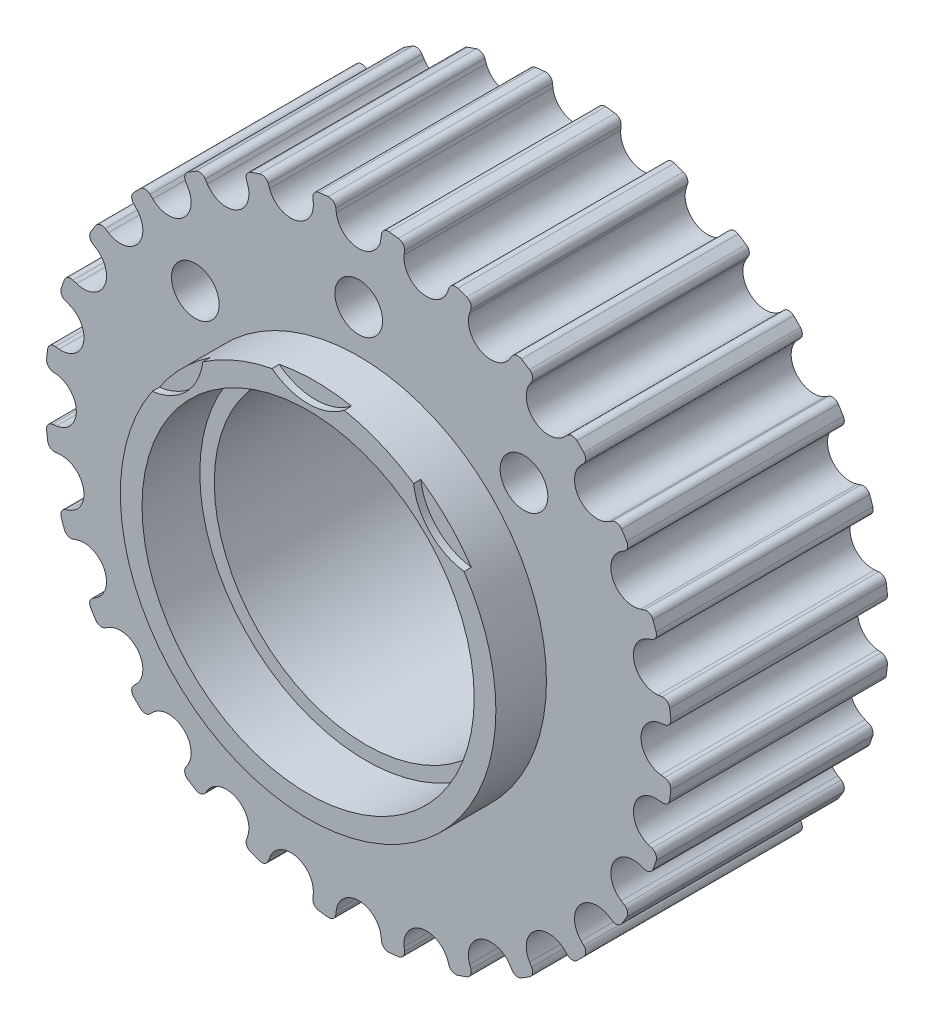
SolidWorks part; units mm, degrees
note: The reader was unsure of these and kept them because the rebuilt part matched: shared geometry of "草图15<2>".
ref_plane "前视基准面" through (0, 0, 0) normal (0, 0, 1) x (1, 0, 0)
ref_plane "上视基准面" through (0, 0, 0) normal (0, 1, 0) x (1, 0, 0)
ref_plane "右视基准面" through (0, 0, 0) normal (1, 0, 0) x (0, 0, -1)
sketch "草图2" plane through (0, 0, 0) normal (0, 0, 1) x (1, 0, 0)
  line L36 (1.3319, 20.7804) -> (1.2989, 20.5118)
  line L37 (-1.7978, 20.5118) -> (-1.8308, 20.7804)
  line L38 (-3.4222, 20.6011) -> (-3.3946, 20.3319)
  line L39 (-6.4137, 19.6428) -> (-6.5056, 19.8973)
  line L40 (-8.0172, 19.3684) -> (-7.9303, 19.1121)
  line L41 (-10.7204, 17.7684) -> (-10.8667, 17.9962)
  line L42 (-12.2227, 17.1441) -> (-12.081, 16.9135)
  line L43 (-14.5021, 14.9827) -> (-14.6954, 15.1722)
  line L44 (-15.8278, 14.0398) -> (-15.6383, 13.8465)
  line L45 (-17.5691, 11.4254) -> (-17.7997, 11.5671)
  line L46 (-18.6517, 10.2111) -> (-18.424, 10.0648)
  line L47 (-19.7676, 7.2748) -> (-20.024, 7.3616)
  line L48 (-20.5529, 5.85) -> (-20.2983, 5.7581)
  line L49 (-20.9874, 2.739) -> (-21.2567, 2.7666)
  line L50 (-21.436, 1.1752) -> (-21.1673, 1.1423)
  line L51 (-21.1673, -1.9545) -> (-21.436, -1.9875)
  line L52 (-21.2567, -3.5789) -> (-20.9874, -3.5512)
  line L53 (-20.2983, -6.5703) -> (-20.5529, -6.6623)
  line L54 (-20.024, -8.1739) -> (-19.7676, -8.087)
  line L55 (-18.424, -10.8771) -> (-18.6517, -11.0234)
  line L56 (-17.7997, -12.3793) -> (-17.5691, -12.2376)
  line L57 (-15.6383, -14.6588) -> (-15.8278, -14.8521)
  line L58 (-14.6954, -15.9845) -> (-14.5021, -15.795)
  line L59 (-12.081, -17.7258) -> (-12.2227, -17.9564)
  line L60 (-10.8667, -18.8084) -> (-10.7204, -18.5807)
  line L61 (-7.9303, -19.9243) -> (-8.0172, -20.1806)
  line L62 (-6.5056, -20.7096) -> (-6.4137, -20.455)
  line L63 (-3.3946, -21.1441) -> (-3.4222, -21.4133)
  line L64 (-1.8308, -21.5926) -> (-1.7978, -21.324)
  line L65 (1.2989, -21.324) -> (1.3319, -21.5926)
  line L66 (2.9233, -21.4133) -> (2.8957, -21.1441)
  line L67 (5.9148, -20.455) -> (6.0067, -20.7096)
  line L68 (7.5183, -20.1806) -> (7.4314, -19.9243)
  line L69 (10.2215, -18.5807) -> (10.3678, -18.8084)
  line L70 (11.7238, -17.9564) -> (11.5821, -17.7258)
  line L71 (14.0032, -15.795) -> (14.1965, -15.9845)
  line L72 (15.3289, -14.8521) -> (15.1394, -14.6588)
  line L73 (17.0702, -12.2376) -> (17.3008, -12.3793)
  line L74 (18.1528, -11.0234) -> (17.9251, -10.8771)
  line L75 (19.2687, -8.087) -> (19.5251, -8.1739)
  line L76 (20.054, -6.6623) -> (19.7994, -6.5703)
  line L77 (20.4885, -3.5512) -> (20.7578, -3.5789)
  line L78 (20.9371, -1.9875) -> (20.6684, -1.9545)
  line L79 (20.6684, 1.1423) -> (20.9371, 1.1752)
  line L80 (20.7578, 2.7666) -> (20.4885, 2.739)
  line L81 (19.7994, 5.7581) -> (20.054, 5.85)
  line L82 (19.5251, 7.3616) -> (19.2687, 7.2748)
  line L83 (17.9251, 10.0648) -> (18.1528, 10.2111)
  line L84 (17.3008, 11.5671) -> (17.0702, 11.4254)
  line L85 (15.1394, 13.8465) -> (15.3289, 14.0398)
  line L86 (14.1965, 15.1722) -> (14.0032, 14.9827)
  line L87 (11.5821, 16.9135) -> (11.7238, 17.1441)
  line L88 (10.3678, 17.9962) -> (10.2215, 17.7684)
  line L89 (7.4314, 19.1121) -> (7.5183, 19.3684)
  line L90 (6.0067, 19.8973) -> (5.9148, 19.6428)
  line L91 (2.8957, 20.3319) -> (2.9233, 20.6011)
  circle A72 centre (-0.2458, -0.3677) radius 12 construction
  circle A73 centre (-0.2458, -0.3677) radius 10.5
  arc A74 (2.9233, 20.6011) -> (2.5067, 21.1262) centre (2.4458, 20.6501) ccw
  arc A75 (2.5067, 21.1262) -> (1.8549, 21.1996) centre (-0.2495, -0.4061) ccw
  arc A76 (1.8549, 21.1996) -> (1.3319, 20.7804) centre (1.8083, 20.7219) ccw
  arc A77 (-1.7978, 20.5118) -> (1.2989, 20.5118) centre (-0.2495, 20.7019) ccw
  arc A78 (-1.8308, 20.7804) -> (-2.3538, 21.1996) centre (-2.3072, 20.7219) ccw
  arc A79 (-2.3538, 21.1996) -> (-3.0056, 21.1262) centre (-0.2495, -0.4061) ccw
  arc A80 (-3.0056, 21.1262) -> (-3.4222, 20.6011) centre (-2.9447, 20.6501) ccw
  arc A81 (-6.4137, 19.6428) -> (-3.3946, 20.3319) centre (-4.9464, 20.1727) ccw
  arc A82 (-6.5056, 19.8973) -> (-7.1087, 20.1897) centre (-6.9571, 19.7343) ccw
  arc A83 (-7.1087, 20.1897) -> (-7.7279, 19.973) centre (-0.2495, -0.4061) ccw
  arc A84 (-7.7279, 19.973) -> (-8.0172, 19.3684) centre (-7.5626, 19.5224) ccw
  arc A85 (-10.7204, 17.7684) -> (-7.9303, 19.1121) centre (-9.4079, 18.6115) ccw
  arc A86 (-10.8667, 17.9962) -> (-11.5198, 18.147) centre (-11.2706, 17.7367) ccw
  arc A87 (-11.5198, 18.147) -> (-12.0752, 17.798) centre (-0.2495, -0.4061) ccw
  arc A88 (-12.0752, 17.798) -> (-12.2227, 17.1441) centre (-11.8137, 17.3954) ccw
  arc A89 (-14.5021, 14.9827) -> (-12.081, 16.9135) centre (-13.4101, 16.0968) ccw
  arc A90 (-14.6954, 15.1722) -> (-15.3656, 15.1739) centre (-15.0314, 14.8294) ccw
  arc A91 (-15.3656, 15.1739) -> (-15.8295, 14.7101) centre (-0.2495, -0.4061) ccw
  arc A92 (-15.8295, 14.7101) -> (-15.8278, 14.0398) centre (-15.485, 14.3758) ccw
  arc A93 (-17.5691, 11.4254) -> (-15.6383, 13.8465) centre (-16.7524, 12.7545) ccw
  arc A94 (-17.7997, 11.5671) -> (-18.4535, 11.4196) centre (-18.051, 11.1582) ccw
  arc A95 (-18.4535, 11.4196) -> (-18.8026, 10.8642) centre (-0.2495, -0.4061) ccw
  arc A96 (-18.8026, 10.8642) -> (-18.6517, 10.2111) centre (-18.3923, 10.615) ccw
  arc A97 (-19.7676, 7.2748) -> (-18.424, 10.0648) centre (-19.2671, 8.7523) ccw
  arc A98 (-20.024, 7.3616) -> (-20.6286, 7.0724) centre (-20.178, 6.907) ccw
  arc A99 (-20.6286, 7.0724) -> (-20.8453, 6.4532) centre (-0.2495, -0.4061) ccw
  arc A100 (-20.8453, 6.4532) -> (-20.5529, 5.85) centre (-20.3899, 6.3015) ccw
  arc A101 (-20.9874, 2.739) -> (-20.2983, 5.7581) centre (-20.8282, 4.2909) ccw
  arc A102 (-21.2567, 2.7666) -> (-21.7818, 2.3501) centre (-21.3057, 2.2891) ccw
  arc A103 (-21.7818, 2.3501) -> (-21.8552, 1.6982) centre (-0.2495, -0.4061) ccw
  arc A104 (-21.8552, 1.6982) -> (-21.436, 1.1752) centre (-21.3775, 1.6517) ccw
  arc A105 (-21.1673, -1.9545) -> (-21.1673, 1.1423) centre (-21.3575, -0.4061) ccw
  arc A106 (-21.436, -1.9875) -> (-21.8552, -2.5104) centre (-21.3775, -2.4639) ccw
  arc A107 (-21.8552, -2.5104) -> (-21.7818, -3.1623) centre (-0.2495, -0.4061) ccw
  arc A108 (-21.7818, -3.1623) -> (-21.2567, -3.5789) centre (-21.3057, -3.1014) ccw
  arc A109 (-20.2983, -6.5703) -> (-20.9874, -3.5512) centre (-20.8282, -5.1031) ccw
  arc A110 (-20.5529, -6.6623) -> (-20.8453, -7.2654) centre (-20.3899, -7.1137) ccw
  arc A111 (-20.8453, -7.2654) -> (-20.6286, -7.8846) centre (-0.2495, -0.4061) ccw
  arc A112 (-20.6286, -7.8846) -> (-20.024, -8.1739) centre (-20.178, -7.7192) ccw
  arc A113 (-18.424, -10.8771) -> (-19.7676, -8.087) centre (-19.2671, -9.5645) ccw
  arc A114 (-18.6517, -11.0234) -> (-18.8026, -11.6764) centre (-18.3923, -11.4272) ccw
  arc A115 (-18.8026, -11.6764) -> (-18.4535, -12.2319) centre (-0.2495, -0.4061) ccw
  arc A116 (-18.4535, -12.2319) -> (-17.7997, -12.3793) centre (-18.051, -11.9704) ccw
  arc A117 (-15.6383, -14.6588) -> (-17.5691, -12.2376) centre (-16.7524, -13.5667) ccw
  arc A118 (-15.8278, -14.8521) -> (-15.8295, -15.5223) centre (-15.485, -15.1881) ccw
  arc A119 (-15.8295, -15.5223) -> (-15.3656, -15.9862) centre (-0.2495, -0.4061) ccw
  arc A120 (-15.3656, -15.9862) -> (-14.6954, -15.9845) centre (-15.0314, -15.6417) ccw
  arc A121 (-12.081, -17.7258) -> (-14.5021, -15.795) centre (-13.4101, -16.909) ccw
  arc A122 (-12.2227, -17.9564) -> (-12.0752, -18.6102) centre (-11.8137, -18.2077) ccw
  arc A123 (-12.0752, -18.6102) -> (-11.5198, -18.9592) centre (-0.2495, -0.4061) ccw
  arc A124 (-11.5198, -18.9592) -> (-10.8667, -18.8084) centre (-11.2706, -18.549) ccw
  arc A125 (-7.9303, -19.9243) -> (-10.7204, -18.5807) centre (-9.4079, -19.4238) ccw
  arc A126 (-8.0172, -20.1806) -> (-7.7279, -20.7853) centre (-7.5626, -20.3347) ccw
  arc A127 (-7.7279, -20.7853) -> (-7.1087, -21.0019) centre (-0.2495, -0.4061) ccw
  arc A128 (-7.1087, -21.0019) -> (-6.5056, -20.7096) centre (-6.9571, -20.5465) ccw
  arc A129 (-3.3946, -21.1441) -> (-6.4137, -20.455) centre (-4.9464, -20.9849) ccw
  arc A130 (-3.4222, -21.4133) -> (-3.0056, -21.9384) centre (-2.9447, -21.4623) ccw
  arc A131 (-3.0056, -21.9384) -> (-2.3538, -22.0119) centre (-0.2495, -0.4061) ccw
  arc A132 (-2.3538, -22.0119) -> (-1.8308, -21.5926) centre (-2.3072, -21.5341) ccw
  arc A133 (1.2989, -21.324) -> (-1.7978, -21.324) centre (-0.2495, -21.5141) ccw
  arc A134 (1.3319, -21.5926) -> (1.8549, -22.0119) centre (1.8083, -21.5341) ccw
  arc A135 (1.8549, -22.0119) -> (2.5067, -21.9384) centre (-0.2495, -0.4061) ccw
  arc A136 (2.5067, -21.9384) -> (2.9233, -21.4133) centre (2.4458, -21.4623) ccw
  arc A137 (5.9148, -20.455) -> (2.8957, -21.1441) centre (4.4475, -20.9849) ccw
  arc A138 (6.0067, -20.7096) -> (6.6098, -21.0019) centre (6.4582, -20.5465) ccw
  arc A139 (6.6098, -21.0019) -> (7.229, -20.7853) centre (-0.2495, -0.4061) ccw
  arc A140 (7.229, -20.7853) -> (7.5183, -20.1806) centre (7.0637, -20.3347) ccw
  arc A141 (10.2215, -18.5807) -> (7.4314, -19.9243) centre (8.909, -19.4238) ccw
  arc A142 (10.3678, -18.8084) -> (11.0209, -18.9592) centre (10.7716, -18.549) ccw
  arc A143 (11.0209, -18.9592) -> (11.5763, -18.6102) centre (-0.2495, -0.4061) ccw
  arc A144 (11.5763, -18.6102) -> (11.7238, -17.9564) centre (11.3148, -18.2077) ccw
  arc A145 (14.0032, -15.795) -> (11.5821, -17.7258) centre (12.9112, -16.909) ccw
  arc A146 (14.1965, -15.9845) -> (14.8667, -15.9862) centre (14.5325, -15.6417) ccw
  arc A147 (14.8667, -15.9862) -> (15.3306, -15.5223) centre (-0.2495, -0.4061) ccw
  arc A148 (15.3306, -15.5223) -> (15.3289, -14.8521) centre (14.9861, -15.1881) ccw
  arc A149 (17.0702, -12.2376) -> (15.1394, -14.6588) centre (16.2534, -13.5667) ccw
  arc A150 (17.3008, -12.3793) -> (17.9546, -12.2319) centre (17.5521, -11.9704) ccw
  arc A151 (17.9546, -12.2319) -> (18.3036, -11.6764) centre (-0.2495, -0.4061) ccw
  arc A152 (18.3036, -11.6764) -> (18.1528, -11.0234) centre (17.8934, -11.4272) ccw
  arc A153 (19.2687, -8.087) -> (17.9251, -10.8771) centre (18.7682, -9.5645) ccw
  arc A154 (19.5251, -8.1739) -> (20.1297, -7.8846) centre (19.6791, -7.7192) ccw
  arc A155 (20.1297, -7.8846) -> (20.3464, -7.2654) centre (-0.2495, -0.4061) ccw
  arc A156 (20.3464, -7.2654) -> (20.054, -6.6623) centre (19.891, -7.1137) ccw
  arc A157 (20.4885, -3.5512) -> (19.7994, -6.5703) centre (20.3293, -5.1031) ccw
  arc A158 (20.7578, -3.5789) -> (21.2829, -3.1623) centre (20.8067, -3.1014) ccw
  arc A159 (21.2829, -3.1623) -> (21.3563, -2.5104) centre (-0.2495, -0.4061) ccw
  arc A160 (21.3563, -2.5104) -> (20.9371, -1.9875) centre (20.8786, -2.4639) ccw
  arc A161 (20.6684, 1.1423) -> (20.6684, -1.9545) centre (20.8585, -0.4061) ccw
  arc A162 (20.9371, 1.1752) -> (21.3563, 1.6982) centre (20.8786, 1.6517) ccw
  arc A163 (21.3563, 1.6982) -> (21.2829, 2.3501) centre (-0.2495, -0.4061) ccw
  arc A164 (21.2829, 2.3501) -> (20.7578, 2.7666) centre (20.8067, 2.2891) ccw
  arc A165 (19.7994, 5.7581) -> (20.4885, 2.739) centre (20.3293, 4.2909) ccw
  arc A166 (20.054, 5.85) -> (20.3464, 6.4532) centre (19.891, 6.3015) ccw
  arc A167 (20.3464, 6.4532) -> (20.1297, 7.0724) centre (-0.2495, -0.4061) ccw
  arc A168 (20.1297, 7.0724) -> (19.5251, 7.3616) centre (19.6791, 6.907) ccw
  arc A169 (17.9251, 10.0648) -> (19.2687, 7.2748) centre (18.7682, 8.7523) ccw
  arc A170 (18.1528, 10.2111) -> (18.3036, 10.8642) centre (17.8934, 10.615) ccw
  arc A171 (18.3036, 10.8642) -> (17.9546, 11.4196) centre (-0.2495, -0.4061) ccw
  arc A172 (17.9546, 11.4196) -> (17.3008, 11.5671) centre (17.5521, 11.1582) ccw
  arc A173 (15.1394, 13.8465) -> (17.0702, 11.4254) centre (16.2534, 12.7545) ccw
  arc A174 (15.3289, 14.0398) -> (15.3306, 14.7101) centre (14.9861, 14.3758) ccw
  arc A175 (15.3306, 14.7101) -> (14.8667, 15.1739) centre (-0.2495, -0.4061) ccw
  arc A176 (14.8667, 15.1739) -> (14.1965, 15.1722) centre (14.5325, 14.8294) ccw
  arc A177 (11.5821, 16.9135) -> (14.0032, 14.9827) centre (12.9112, 16.0968) ccw
  arc A178 (11.7238, 17.1441) -> (11.5763, 17.798) centre (11.3148, 17.3954) ccw
  arc A179 (11.5763, 17.798) -> (11.0209, 18.147) centre (-0.2495, -0.4061) ccw
  arc A180 (11.0209, 18.147) -> (10.3678, 17.9962) centre (10.7716, 17.7367) ccw
  arc A181 (7.4314, 19.1121) -> (10.2215, 17.7684) centre (8.909, 18.6115) ccw
  arc A182 (7.5183, 19.3684) -> (7.229, 19.973) centre (7.0637, 19.5224) ccw
  arc A183 (7.229, 19.973) -> (6.6098, 20.1897) centre (-0.2495, -0.4061) ccw
  arc A184 (6.6098, 20.1897) -> (6.0067, 19.8973) centre (6.4582, 19.7343) ccw
  arc A185 (2.8957, 20.3319) -> (5.9148, 19.6428) centre (4.4475, 20.1727) ccw
extrude "凸台-拉伸1" add sketch "草图2" along normal blind 15
move or copy body "实体-移动/复制1" bodies to move or copy 106 copy no translate (-21.7751, 0, 0)
sketch "草图12" plane through (0, 0, 15) normal (0, 0, 1) x (1, 0, 0)
  circle A0 centre (-22.0209, -0.3677) radius 10.5 construction
  circle A1 centre (-22.0209, -0.3677) radius 10.5
  circle A2 centre (-22.0246, -0.3096) radius 11.5
  circle A3 centre (-22.0246, -0.3096) radius 13
  circle A4 centre (-22.0209, -0.3677) radius 16
  point P7 (-6.0209, -0.3677)
  point P10 (-10.7072, -11.6815)
  point P11 (-22.0209, -16.3677)
  point P12 (-33.3346, -11.6815)
  point P13 (-38.0209, -0.3677)
  point P14 (-33.3346, 10.946)
  point P15 (-22.0209, 15.6323)
  point P16 (-10.7072, 10.946)
  point P17 (-22.0209, -0.3677)
  dimension "D1" = 23
  dimension "D2" = 26
  dimension "D3" = 32
  dimension "D4" = 8
extrude "凸台-拉伸2" add sketch "草图12" along normal blind 3.5 and the other way blind 19.5 contours A3 A2
hole_wizard "M4 螺纹孔1" positions "3D草图1" profile "草图13" tap size "M4" standard "GB" end condition through all
sketch3d "3D草图1"
  circle A0 centre (-22.0209, -0.3677, 15) radius 16 construction
  point P0 (-33.3346, 10.946, 15)
  point P3 (-22.0209, 15.6323, 15)
  point P6 (-10.5793, 10.8166, 15)
  point P10 (-22.0209, -0.3677, 31)
cosmetic thread "孔螺蚊线4" parameters "D2"=4
cosmetic thread "孔螺蚊线5" parameters "D2"=4
cosmetic thread "孔螺蚊线6" parameters "D2"=4
sketch "草图13" plane through (-33.3346, 10.946, 15) normal (1, 0, 0) x (0, -1, 0)
  line L0 (0, 0) -> (0, 19.5)
  line L1 (0, 19.5) -> (1.65, 19.5)
  line L2 (1.65, 19.5) -> (1.65, 0)
  line L5 (1.65, 0) -> (0, 0)
  line L11 (0, -6.35) -> (0, 107.95) construction
  dimension "通孔螺纹孔钻头直径" = 3.3
  dimension "通孔螺纹孔钻头深度" = 19.5
sketch "草图14" plane through (0, 0, 15) normal (0, 0, 1) x (1, 0, 0)
  circle A0 centre (-22.0209, -0.3677) radius 10.5 construction
  circle A1 centre (-22.0246, -0.3096) radius 11.5
  circle A2 centre (-22.0246, -0.3096) radius 11.5
  circle A3 centre (-22.0209, -0.3677) radius 10.5
  dimension "D1" = 0
extrude "切除-拉伸1" cut sketch "草图14" against normal blind 0.5
sketch "草图15" plane through (0, 0, 15) normal (0, 0, 1) x (1, 0, 0)
  circle A0 centre (-22.0209, -0.3677) radius 16 construction
  circle A1 centre (-22.0209, -0.3677) radius 16 construction
  circle A2 centre (-22.0209, 15.6323) radius 4.05
  circle A3 centre (-10.7072, 10.946) radius 4.05
  circle A4 centre (-6.0209, -0.3677) radius 4.05 [skipped]
  circle A8 centre (-38.0209, -0.3677) radius 4.05 [skipped]
  circle A9 centre (-33.3346, 10.946) radius 4.05
  circle A10 centre (-10.7072, -11.6815) radius 4.05 [skipped]
  circle A11 centre (-33.3346, -11.6815) radius 4.05 [skipped]
  circle A12 centre (-22.0209, -16.3677) radius 4.05 [skipped]
  point P0 (-33.3346, -11.6815)
  point P2 (-22.0209, -16.3677)
  point P4 (-10.7072, -11.6815)
  point P6 (-10.7072, 10.946)
  point P8 (-22.0209, 15.6323)
  point P10 (-33.3346, 10.946)
  point P34 (-22.0209, -0.3677)
  dimension "D1" = 8.1
  dimension "D2" = 8
extrude "切除-拉伸2" cut sketch "草图15" against normal blind 0.5 from surface at 3.5 starting at face at (-10.5246, -0.3096, 18.5)
extrude "切除-拉伸3" cut sketch "草图15<2>" along normal blind 1.5 from surface at -19.5
sketch "草图15<2>" plane through (0, 0, 15) normal (0, 0, 1) x (1, 0, 0) same geometry as "草图15"
sketch "草图16" plane through (0, 0, 0) normal (0, 0, -1) x (-1, 0, 0)
  circle A0 centre (22.0209, -0.3677) radius 10.5 construction
  circle A1 centre (22.0246, -0.3096) radius 11.5
  circle A2 centre (22.0246, -0.3096) radius 11.5
  circle A3 centre (22.0209, -0.3677) radius 10.5
  dimension "D1" = 0
extrude "凸台-拉伸3" add sketch "草图16" along normal blind 0.5
